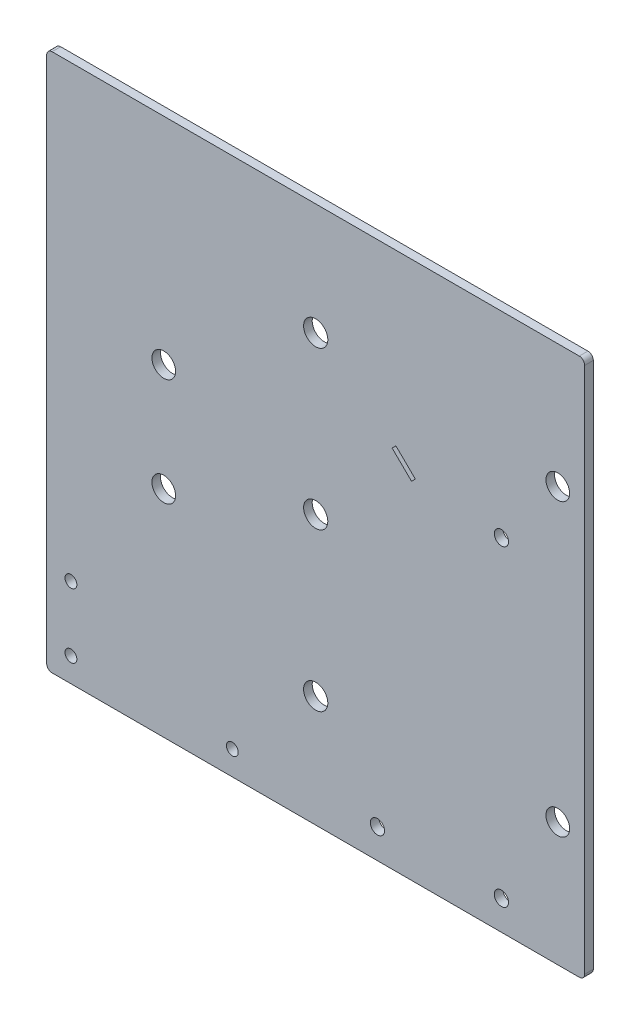
SolidWorks part; units mm, degrees
material "FR4_stuffedProtoboard"
ref_plane "Front Plane" through (0, 0, 0) normal (0, 0, 1) x (1, 0, 0)
ref_plane "Top Plane" through (0, 0, 0) normal (0, 1, 0) x (1, 0, 0)
ref_plane "Right Plane" through (0, 0, 0) normal (1, 0, 0) x (0, 0, -1)
sketch "Sketch1" plane through (0, 0, 0) normal (0, 0, 1) x (1, 0, 0)
  line L1 (-50, -50) -> (50, -50)
  line L2 (-50, -50) -> (-50, 50)
  line L3 (-50, 50) -> (50, 50)
  line L4 (50, -50) -> (50, 50)
  line L5 (-50, -50) -> (50, 50) construction
  line L6 (-50, 50) -> (50, -50) construction
  dimension "D1" = 100
extrude "Boss-Extrude1" add sketch "Sketch1" along normal blind 1.6
sketch "Sketch2" [suppressed] plane through (0, 0, 1.6) normal (0, 0, 1) x (1, 0, 0)
  circle A0 centre (0, 0) radius 50
  line M2 (50, -50) -> (50, 50)
  line M3 (50, 50) -> (-50, 50)
  line M4 (-50, 50) -> (-50, -50)
  line M5 (-50, -50) -> (50, -50)
  dimension "D1" = 100
extrude "Cut-Extrude1" [suppressed] cut sketch "Sketch2" against normal blind 1.6 contours A0 M3 M4 | A0 M4 M5 | A0 M5 M2 | A0 M2 M3
sketch "Sketch3" plane through (0, 0, 1.6) normal (0, 0, -1) x (-1, 0, 0)
  line L0 (-40, -22) -> (-50, -22) construction
  line L1 (-40, -32) -> (-40, -22) construction
  line L2 (-50, -32) -> (-40, -32) construction
  line L3 (-50, -22) -> (-50, -32) construction
  line L4 (-40, -22) -> (-50, -22)
  line L5 (-40, -32) -> (-40, -22)
  line L6 (-50, -32) -> (-40, -32)
  line L7 (-50, -22) -> (-50, -32)
  line L8 (-40, 22) -> (-40, 32) construction
  line L9 (-40, 32) -> (-50, 32) construction
  line L10 (-50, 32) -> (-50, 22) construction
  line L11 (-50, 22) -> (-40, 22) construction
  line L12 (-40, 22) -> (-40, 32)
  line L13 (-40, 32) -> (-50, 32)
  line L14 (-50, 32) -> (-50, 22)
  line L15 (-50, 22) -> (-40, 22)
  line L32 (17.2447, 25) -> (45.2447, 25) construction
  line L33 (45.2447, 25) -> (45.2447, -25) construction
  line L34 (17.2447, -25) -> (45.2447, -25) construction
  line L35 (17.2447, 25) -> (17.2447, -25) construction
  line L36 (17.2447, 25) -> (45.2447, 25)
  line L37 (45.2447, 25) -> (45.2447, -25)
  line L38 (17.2447, -25) -> (45.2447, -25)
  line L39 (17.2447, 25) -> (17.2447, -25)
  circle A3 centre (0, 0) radius 2.2479
  circle A4 centre (-34.525, -44.525) radius 1.325 construction
  circle A6 centre (-34.525, -44.525) radius 1.325
  circle A10 centre (0, -29.25) radius 2.25
  circle A11 centre (-45, -27) radius 2.2
  circle A12 centre (0, 29.25) radius 2.25
  circle A13 centre (-45, 27) radius 2.2
  circle A14 centre (-34.525, 13.525) radius 1.325 construction
  circle A15 centre (-34.525, 13.525) radius 1.325
  circle A16 centre (15.5, -45.5) radius 1.1 construction
  circle A17 centre (15.5, -45.5) radius 1.1
  circle A18 centre (45.5, -45.5) radius 1.1 construction
  circle A19 centre (45.5, -45.5) radius 1.1
  circle A20 centre (45.5, -33.5) radius 1.1 construction
  circle A21 centre (45.5, -33.5) radius 1.1
  circle A22 centre (-11.475, -44.525) radius 1.325 construction
  circle A23 centre (-11.475, -44.525) radius 1.325
  circle A24 centre (28.2447, -9.9994) radius 2.2 construction
  circle A25 centre (28.2447, -9.9994) radius 2.2
  circle A26 centre (28.2447, 10.0006) radius 2.2 construction
  circle A27 centre (28.2447, 10.0006) radius 2.2
  circle A28 centre (-45, 27) radius 2.2 construction
  circle A29 centre (-45, 27) radius 2.2
  circle A30 centre (-45, -27) radius 2.2 construction
  circle A31 centre (-45, -27) radius 2.2
  dimension "D1" = 4.4958
extrude "Cut-Extrude2" cut sketch "Sketch3" along normal through all contours A13 | A11 | A3 | A15 | A6 | A23 | A27 | A25 | A17 | A21 | A19 | A12 | A10 region at (0, 0, 1.6) region at (34.525, -44.525, 1.6) region at (45, -27, 1.6) region at (45, 27, 1.6) region at (34.525, 13.525, 1.6) region at (-15.5, -45.5, 1.6) region at (-45.5, -45.5, 1.6) region at (-45.5, -33.5, 1.6) region at (11.475, -44.525, 1.6) region at (-28.2447, -9.9994, 1.6) region at (-28.2447, 10.0006, 1.6)
sketch "Sketch4" plane through (0, 0, 1.6) normal (0, 0, 1) x (1, 0, 0)
  line L0 (38, -44.25) -> (38, -18.925) construction
  line L5 (38, -44.25) -> (38, -18.925)
  line L6 (11.75, -48) -> (34.25, -48) construction
  line L7 (11.75, -48) -> (34.25, -48)
  line L8 (8, -44.25) -> (8, 13.25) construction
  line L9 (8, -44.25) -> (8, 13.25)
  line L11 (33, -3) -> (33, -48) construction
  line L13 (34.25, 17) -> (11.75, 17)
  line L14 (38, 13.25) -> (38, -18.925)
  line L15 (-48, -48) -> (-13, -48) construction
  line L16 (-48, -48) -> (-13, -48)
  line L17 (-48, -31) -> (-48, -48) construction
  line L18 (-48, -31) -> (-48, -48)
  line L19 (-13, -40.5) -> (-13, -32.5) construction
  line L20 (-13, -40.5) -> (-13, -32.5)
  line L21 (-13, -48) -> (-13, -40.5) construction
  line L22 (-13, -48) -> (-13, -40.5)
  line L23 (-13, -32.5) -> (-13, -31) construction
  line L24 (-13, -32.5) -> (-13, -31)
  line L25 (-13, -31) -> (-48, -31) construction
  line L26 (-13, -31) -> (-48, -31)
  line L27 (-20, -34) -> (-20, -48) construction
  arc A0 (34.25, -48) -> (38, -44.25) centre (34.25, -44.25) ccw construction
  arc A1 (34.25, -48) -> (38, -44.25) centre (34.25, -44.25) ccw
  arc A2 (8, -44.25) -> (11.75, -48) centre (11.75, -44.25) ccw construction
  arc A3 (8, -44.25) -> (11.75, -48) centre (11.75, -44.25) ccw
  arc A4 (11.75, 17) -> (8, 13.25) centre (11.75, 13.25) ccw construction
  arc A5 (11.75, 17) -> (8, 13.25) centre (11.75, 13.25) ccw
  arc A6 (38, 13.25) -> (34.25, 17) centre (34.25, 13.25) ccw construction
  arc A7 (38, 13.25) -> (34.25, 17) centre (34.25, 13.25) ccw
  text T0 "Raspberry Pi Zero W" font "Century Gothic" height 2
  text T1 "Atheros" font "Century Gothic" height 2
  dimension "D1" = 5
  dimension "D2" = 20
  dimension "D3" = 3
  dimension "D4" = 7
fillet "Fillet1" radius 1 4 edges at (-50, -50, 0.8) (-50, 50, 0.8) (50, -50, 0.8) (50, 50, 0.8)
sketch "Sketch5" plane through (0, 0, 0) normal (0, 0, -1) x (-1, 0, 0)
  line L16 (-14.2075, 17.7955) -> (-17.8185, 14.2525)
  line L17 (-17.8185, 14.2525) -> (-18.5188, 14.9663)
  line L18 (-18.5188, 14.9663) -> (-14.9078, 18.5093)
  line L19 (-14.9078, 18.5093) -> (-14.2075, 17.7955)
  line L20 (-16.7133, 16.7378) -> (-13.0663, 13.0208) construction
  spline S1 degree 3 poles (-15.4367, 15.4367) (-16.4808, 14.8306) (-17.4743, 14.1392) (-18.4059, 13.3713) knots 0 0 0 0 1 1 1 1 construction
extrude "Cut-Extrude4" cut sketch "Sketch5" against normal through all contours L18 L19 L16 L17
